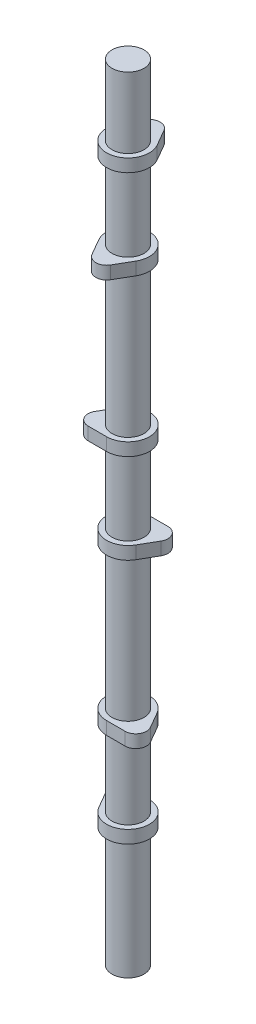
SolidWorks part; units mm, degrees
note: '?' marks a value the reader was unsure of.
ref_plane "Front Plane" through (0, 0, 0) normal (0, 0, 1) x (1, 0, 0)
ref_plane "Top Plane" through (0, 0, 0) normal (0, 1, 0) x (1, 0, 0)
ref_plane "Right Plane" through (0, 0, 0) normal (1, 0, 0) x (0, 0, -1)
sketch "Sketch1" plane through (0, 0, 0) normal (0, 1, 0) x (1, 0, 0)
  line L0 (-5.4993, 15.875) -> (-10.9985, 6.35)
  line L1 (5.4993, 15.875) -> (10.9985, 6.35)
  arc A0 (-10.9985, 6.35) -> (10.9985, 6.35) centre (0, 0) ccw
  arc A1 (5.4993, 15.875) -> (-5.4993, 15.875) centre (0, 12.7) ccw
  dimension "D2" = 12.7
  dimension "D3" = 25.4
  dimension "D1" = 12.7
extrude "Boss-Extrude1" add sketch "Sketch1" along normal blind 7.62
ref_axis "Axis1" through (0, 29.8484, 0) along (0, -1, 0)?
pattern_linear "LPattern1" count 2 spacing 53.34 along (0, -1, 0) of bodies 101
move or copy body "Body-Move/Copy1" bodies to move or copy 102 copy no rotation origin (0, 0, 0) rotation axis (0, 1, 0) rotation angle 180
pattern_linear "LPattern2" count 3 spacing 146.05 along (0, -1, 0) of bodies 103 101
move or copy body "Body-Move/Copy2" bodies to move or copy 106 104 copy no rotation origin (0, 0, 0) rotation axis (0, 1, 0) rotation angle 120
move or copy body "Body-Move/Copy3" bodies to move or copy 105 107 copy no rotation origin (0, 0, 0) rotation axis (0, -1, 0) rotation angle 120
sketch "Sketch2" plane through (0, 0, 0) normal (0, 1, 0) x (1, 0, 0)
  circle A0 centre (0, 0) radius 9.5
  dimension "D1" = 19
extrude "Boss-Extrude2" add sketch "Sketch2" against normal blind 466.09 from offset 49.53
